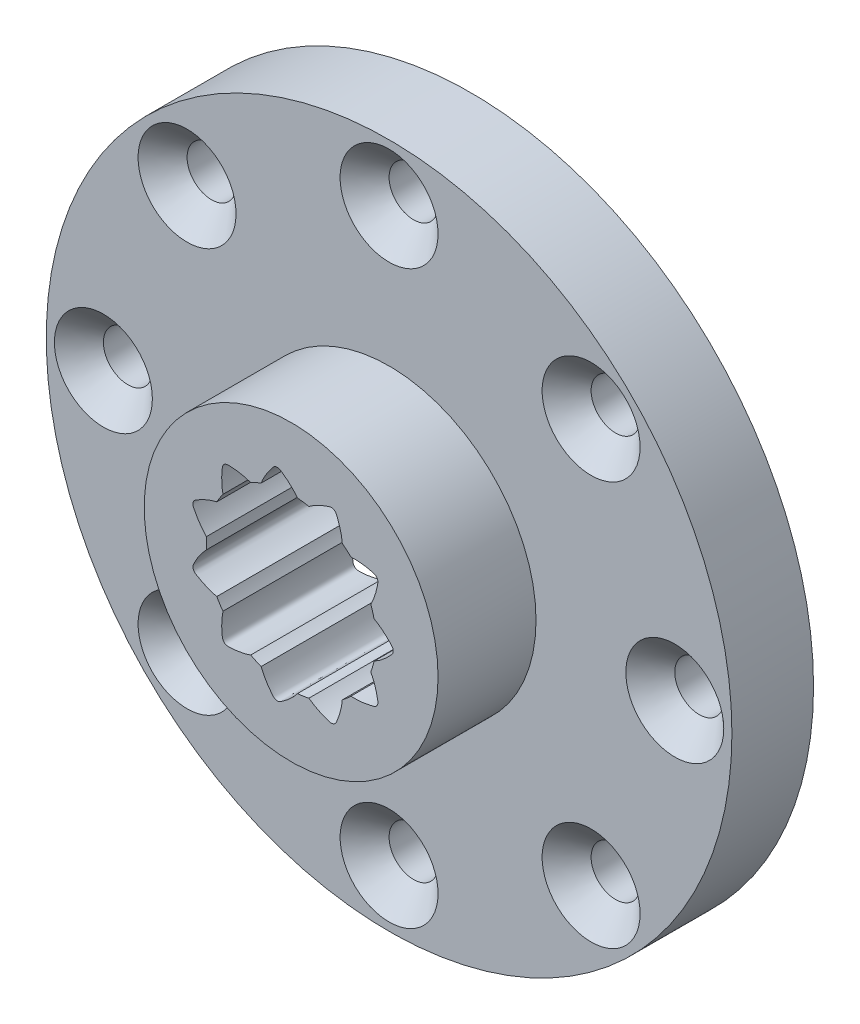
SolidWorks part; units mm, degrees
material "合金钢"
ref_plane "前视基准面" through (0, 0, 0) normal (0, 0, 1) x (1, 0, 0)
ref_plane "上视基准面" through (0, 0, 0) normal (0, 1, 0) x (1, 0, 0)
ref_plane "右视基准面" through (0, 0, 0) normal (1, 0, 0) x (0, 0, -1)
ref_axis "基准轴1" through (0, 0, 55) along (0, 0, -1)
sketch "旋转草图内花键" plane through (0, 0, 0) normal (1, 0, 0) x (0, 0, -1)
  line L0 (0, 0) -> (1, 0) construction
  line L1 (-12.7, 5.2) -> (-12.7, 19.05)
  line L2 (-12.7, 19.05) -> (12.7, 19.05)
  line L3 (12.7, 19.05) -> (12.7, 5.2)
  line L4 (12.7, 5.2) -> (-12.7, 5.2)
revolve "内花键" add sketch "旋转草图内花键" angle 360 about L0
sketch "齿草图内花键" plane through (0, 0, 0) normal (0, 0, 1) x (1, 0, 0)
  arc A0 (4.469, -1.3848) -> (4.469, 1.3848) centre (0, 0) ccw
  spline S0 degree 3 poles (4.469, 1.3848) (4.5766, 1.3527) (4.7413, 1.292) (4.9613, 1.1888) (5.1395, 1.0919) (5.3233, 0.9774) (5.5112, 0.8441) (5.7013, 0.6912) (5.8934, 0.5188) (6.0538, 0.3498) (6.1648, 0.2366) (6.2079, 0.1723) (6.2223, 0.1454) (6.2343, 0.1173) (6.2438, 0.0883) (6.257, 0.0305) (6.257, -0.0305) (6.2438, -0.0883) (6.2343, -0.1173) (6.2223, -0.1454) (6.2079, -0.1723) (6.1648, -0.2366) (6.0538, -0.3498) (5.8934, -0.5188) (5.7013, -0.6912) (5.5112, -0.8441) (5.3233, -0.9774) (5.1395, -1.0919) (4.9613, -1.1888) (4.7413, -1.292) (4.5766, -1.3527) (4.469, -1.3848) knots 0 0 0 0 0.072254 0.112805 0.156306 0.202756 0.252156 0.304505 0.359804 0.418052 0.454758 0.461299 0.467839 0.47438 0.48092 0.487461 0.512539 0.51908 0.52562 0.532161 0.538701 0.545242 0.581948 0.640196 0.695495 0.747844 0.797244 0.843694 0.887195 0.927746 1 1 1 1
extrude "齿拉伸切除内花键" cut sketch "齿草图内花键" against normal blind 12.7 and the other way blind 12.7
pattern_circular "齿形内花键" count 11 over 360 about axis through (0, 0, 55) along (0, 0, -1) of "齿拉伸切除内花键"
sketch "辅助草图内花键" plane through (0, 0, 0) normal (0, 0, 1) x (1, 0, 0)
  circle A0 centre (0, 0) radius 5.5 construction
  circle A1 centre (0, 0) radius 6.06 construction
  dimension "PitchDiameter" = 11
  dimension "FormDiameter" = 12.12
sketch "草图2" plane through (0, 0, -12.7) normal (0, 0, -1) x (-1, 0, 0)
  circle A0 centre (0, 0) radius 19.05 construction
  circle A1 centre (0, 0) radius 19.05
extrude "切除-拉伸1" cut sketch "草图2" against normal blind 16.4
sketch "草图3" plane through (0, 0, 3.7) normal (0, 0, -1) x (-1, 0, 0)
  circle A0 centre (0, 0) radius 14.5
  circle A1 centre (0, 0) radius 19.05
  dimension "D1" = 29
extrude "切除-拉伸3" cut sketch "草图3" against normal through all
sketch "草图4" plane through (0, 0, 12.7) normal (0, 0, 1) x (1, 0, 0)
  circle A0 centre (0, 0) radius 8
  circle A1 centre (0, 0) radius 14.5
  dimension "D1" = 16
extrude "切除-拉伸4" cut sketch "草图4" against normal blind 5
sketch "草图7" plane through (0, 0, 3.7) normal (0, 0, -1) x (-1, 0, 0)
  circle A1 centre (0, 0) radius 14.5
  circle A2 centre (0, 0) radius 14.5
  dimension "D1" = 0
extrude "切除-拉伸6" cut sketch "草图7" against normal blind 1
sketch "草图9" plane through (0, 0, 4.7) normal (0, 0, -1) x (-1, 0, 0)
  circle A0 centre (0, 0) radius 17.5 construction
  circle A1 centre (0, 17.5) radius 1.5
  circle A2 centre (12.3744, 12.3744) radius 1.5
  circle A3 centre (17.5, 0) radius 1.5
  circle A4 centre (12.3744, -12.3744) radius 1.5
  circle A5 centre (0, -17.5) radius 1.5
  circle A6 centre (-12.3744, -12.3744) radius 1.5
  circle A7 centre (-17.5, 0) radius 1.5
  circle A8 centre (-12.3744, 12.3744) radius 1.5
  circle A9 centre (0, 0) radius 21
  point P21 (0, 0)
  dimension "D1" = 35
  dimension "D2" = 3
  dimension "D4" = 42
  dimension "D3" = 8
extrude "凸台-拉伸1" add sketch "草图9" along normal blind 3
sketch "草图12" plane through (0, 0, 7.7) normal (0, 0, 1) x (1, 0, 0)
  circle A0 centre (0, 0) radius 8 construction
  circle A1 centre (0, 0) radius 14.5
  circle A2 centre (0, 0) radius 14.5
  circle A3 centre (0, 0) radius 8
  dimension "D1" = 0
extrude "切除-拉伸8" cut sketch "草图12" against normal up to surface (3 mm away) up to face at (10.8744, 12.3744, 4.7)
sketch "草图13" plane through (0, 0, 4.7) normal (0, 0, 1) x (1, 0, 0)
  arc A11 (-4.5541, -2.51) -> (-4.175, -3.0999) centre (0, 0) ccw
  arc A12 (-2.4742, -4.5737) -> (-1.8363, -4.865) centre (0, 0) ccw
  arc A13 (0.3913, -5.1853) -> (1.0854, -5.0855) centre (0, 0) ccw
  arc A14 (3.1326, -4.1505) -> (3.6625, -3.6914) centre (0, 0) ccw
  arc A15 (4.8792, -1.7981) -> (5.0768, -1.1253) centre (0, 0) ccw
  arc A16 (5.0768, 1.1253) -> (4.8792, 1.7981) centre (0, 0) ccw
  arc A17 (3.6625, 3.6914) -> (3.1326, 4.1505) centre (0, 0) ccw
  arc A18 (1.0854, 5.0855) -> (0.3913, 5.1853) centre (0, 0) ccw
  arc A19 (-1.8363, 4.865) -> (-2.4742, 4.5737) centre (0, 0) ccw
  arc A20 (-4.175, 3.0999) -> (-4.5541, 2.51) centre (0, 0) ccw
  arc A21 (-5.1882, 0.3506) -> (-5.1882, -0.3506) centre (0, 0) ccw
  arc A22 (-4.5541, -2.51) -> (-4.175, -3.0999) centre (0, 0) ccw
  arc A23 (-2.4742, -4.5737) -> (-1.8363, -4.865) centre (0, 0) ccw
  arc A24 (0.3913, -5.1853) -> (1.0854, -5.0855) centre (0, 0) ccw
  arc A25 (3.1326, -4.1505) -> (3.6625, -3.6914) centre (0, 0) ccw
  arc A26 (4.8792, -1.7981) -> (5.0768, -1.1253) centre (0, 0) ccw
  arc A27 (5.0768, 1.1253) -> (4.8792, 1.7981) centre (0, 0) ccw
  arc A28 (3.6625, 3.6914) -> (3.1326, 4.1505) centre (0, 0) ccw
  arc A29 (1.0854, 5.0855) -> (0.3913, 5.1853) centre (0, 0) ccw
  arc A30 (-1.8363, 4.865) -> (-2.4742, 4.5737) centre (0, 0) ccw
  arc A31 (-4.175, 3.0999) -> (-4.5541, 2.51) centre (0, 0) ccw
  arc A32 (-5.1882, 0.3506) -> (-5.1882, -0.3506) centre (0, 0) ccw
  spline S11 degree 3 poles (506.9828, -3964.9614) (126.511, -73.8344) (7.0446, 13.3904) (-5.383, -0.562) (-5.5258, -0.7427) (-5.6651, -0.9431) (-5.8009, -1.1625) (-5.9071, -1.37) (-5.9817, -1.5098) (-6.005, -1.5837) (-6.0112, -1.6136) (-6.0149, -1.6439) (-6.0157, -1.6744) (-6.0122, -1.7336) (-5.995, -1.792) (-5.966, -1.8438) (-5.9488, -1.869) (-5.9293, -1.8925) (-5.9079, -1.9143) (-5.8484, -1.9638) (-5.71, -2.0411) (-5.5085, -2.1582) (-5.2757, -2.2695) (-5.0501, -2.3626) (-4.8323, -2.4375) (13.1656, -7.4562) (66.5095, 130.5093) (-1717.0974, 3609.5914) knots -11.769614 -11.769614 -11.769614 -11.769614 0.156306 0.202756 0.252156 0.304505 0.359804 0.418052 0.454758 0.461299 0.467839 0.47438 0.48092 0.487461 0.512539 0.51908 0.52562 0.532161 0.538701 0.545242 0.581948 0.640196 0.695495 0.747844 0.797244 0.843694 12.769566 12.769566 12.769566 12.769566 only from (-5.1882, -0.3506) to (-4.5541, -2.51)
  spline S12 degree 3 poles (2570.1211, -3061.4422) (146.3457, 6.2836) (-1.3132, 15.0733) (-4.2246, -3.383) (-4.247, -3.6123) (-4.256, -3.8562) (-4.2515, -4.1142) (-4.2287, -4.3461) (-4.2159, -4.5041) (-4.1955, -4.5788) (-4.1846, -4.6073) (-4.1713, -4.6348) (-4.1555, -4.6609) (-4.1205, -4.7088) (-4.0745, -4.7487) (-4.0221, -4.7765) (-3.994, -4.7884) (-3.9649, -4.7977) (-3.9351, -4.8044) (-3.8583, -4.814) (-3.7001, -4.8042) (-3.4672, -4.7937) (-3.2112, -4.7614) (-2.9711, -4.7179) (-2.7474, -4.6631) (15.1067, 0.8453) (-14.6073, 145.7492) (-3396.0067, 2108.2486) knots -11.769614 -11.769614 -11.769614 -11.769614 0.156306 0.202756 0.252156 0.304505 0.359804 0.418052 0.454758 0.461299 0.467839 0.47438 0.48092 0.487461 0.512539 0.51908 0.52562 0.532161 0.538701 0.545242 0.581948 0.640196 0.695495 0.747844 0.797244 0.843694 12.769566 12.769566 12.769566 12.769566 only from (-4.175, -3.0999) to (-2.4742, -4.5737)
  spline S13 degree 3 poles (3817.2641, -1185.9367) (119.7167, 84.4065) (-9.254, 11.9705) (-1.725, -5.13) (-1.6199, -5.335) (-1.4956, -5.5449) (-1.3523, -5.7596) (-1.2077, -5.9424) (-1.1115, -6.0684) (-1.054, -6.1202) (-1.0294, -6.1383) (-1.0033, -6.1542) (-0.9759, -6.1676) (-0.9206, -6.189) (-0.8603, -6.1977) (-0.8012, -6.1928) (-0.7711, -6.1876) (-0.7417, -6.1797) (-0.713, -6.1692) (-0.6432, -6.1357) (-0.5153, -6.042) (-0.3252, -5.9073) (-0.1272, -5.7417) (0.0512, -5.5752) (0.2098, -5.4082) (12.2516, 8.8785) (-91.0864, 114.7147) (-3996.7079, -62.4482) knots -11.769614 -11.769614 -11.769614 -11.769614 0.156306 0.202756 0.252156 0.304505 0.359804 0.418052 0.454758 0.461299 0.467839 0.47438 0.48092 0.487461 0.512539 0.51908 0.52562 0.532161 0.538701 0.545242 0.581948 0.640196 0.695495 0.747844 0.797244 0.843694 12.769566 12.769566 12.769566 12.769566 only from (-1.8363, -4.865) to (0.3913, -5.1853)
  spline S14 degree 3 poles (3852.4527, 1066.0953) (55.0785, 135.731) (-14.2567, 5.0672) (1.3223, -5.2482) (1.5216, -5.3638) (1.7397, -5.4733) (1.9763, -5.5764) (2.1967, -5.652) (2.3457, -5.706) (2.4222, -5.7185) (2.4526, -5.7204) (2.4831, -5.7197) (2.5135, -5.7162) (2.5715, -5.7043) (2.627, -5.6789) (2.674, -5.6429) (2.6965, -5.6222) (2.7171, -5.5996) (2.7356, -5.5754) (2.7762, -5.5094) (2.833, -5.3614) (2.9202, -5.1453) (2.9972, -4.899) (3.0573, -4.6625) (3.1004, -4.4362) (5.5066, 14.0927) (-138.6462, 47.2591) (-3328.4825, -2213.3182) knots -11.769614 -11.769614 -11.769614 -11.769614 0.156306 0.202756 0.252156 0.304505 0.359804 0.418052 0.454758 0.461299 0.467839 0.47438 0.48092 0.487461 0.512539 0.51908 0.52562 0.532161 0.538701 0.545242 0.581948 0.640196 0.695495 0.747844 0.797244 0.843694 12.769566 12.769566 12.769566 12.769566 only from (1.0854, -5.0855) to (3.1326, -4.1505)
  spline S15 degree 3 poles (2664.5148, 2979.6496) (-27.0468, 143.9618) (-14.733, -3.445) (3.9498, -3.7002) (4.1799, -3.6897) (4.4226, -3.6639) (4.6773, -3.6227) (4.9037, -3.5672) (5.0582, -3.532) (5.1293, -3.5012) (5.156, -3.4863) (5.1812, -3.4692) (5.2049, -3.4499) (5.2473, -3.4084) (5.2802, -3.3572) (5.3003, -3.3014) (5.3081, -3.2719) (5.3131, -3.2418) (5.3156, -3.2113) (5.3141, -3.1339) (5.2819, -2.9787) (5.2384, -2.7497) (5.17, -2.5009) (5.0927, -2.2694) (5.0066, -2.0558) (-2.9866, 14.8326) (-142.1868, -35.2009) (-1603.4875, -3661.4753) knots -11.769614 -11.769614 -11.769614 -11.769614 0.156306 0.202756 0.252156 0.304505 0.359804 0.418052 0.454758 0.461299 0.467839 0.47438 0.48092 0.487461 0.512539 0.51908 0.52562 0.532161 0.538701 0.545242 0.581948 0.640196 0.695495 0.747844 0.797244 0.843694 12.769566 12.769566 12.769566 12.769566 only from (3.6625, -3.6914) to (4.8792, -1.7981)
  spline S16 degree 3 poles (630.6123, 3947.1862) (-100.5848, 106.4858) (-10.5317, -10.8634) (5.3233, -0.9774) (5.5112, -0.8441) (5.7013, -0.6912) (5.8934, -0.5188) (6.0538, -0.3498) (6.1648, -0.2366) (6.2079, -0.1723) (6.2223, -0.1454) (6.2343, -0.1173) (6.2438, -0.0883) (6.257, -0.0305) (6.257, 0.0305) (6.2438, 0.0883) (6.2343, 0.1173) (6.2223, 0.1454) (6.2079, 0.1723) (6.1648, 0.2366) (6.0538, 0.3498) (5.8934, 0.5188) (5.7013, 0.6912) (5.5112, 0.8441) (5.3233, 0.9774) (-10.5317, 10.8633) (-100.5841, -106.4849) (630.6034, -3947.1398) knots -11.769614 -11.769614 -11.769614 -11.769614 0.156306 0.202756 0.252156 0.304505 0.359804 0.418052 0.454758 0.461299 0.467839 0.47438 0.48092 0.487461 0.512539 0.51908 0.52562 0.532161 0.538701 0.545242 0.581948 0.640196 0.695495 0.747844 0.797244 0.843694 12.769566 12.769566 12.769566 12.769566 only from (5.0768, -1.1253) to (5.0768, 1.1253)
  spline S17 degree 3 poles (-1603.5052, 3661.5191) (-142.1879, 35.2013) (-2.9867, -14.8327) (5.0066, 2.0558) (5.0927, 2.2694) (5.17, 2.5009) (5.2384, 2.7497) (5.2819, 2.9787) (5.3141, 3.1339) (5.3156, 3.2113) (5.3131, 3.2418) (5.3081, 3.2719) (5.3003, 3.3014) (5.2802, 3.3572) (5.2473, 3.4084) (5.2049, 3.4499) (5.1812, 3.4692) (5.156, 3.4863) (5.1293, 3.5012) (5.0582, 3.532) (4.9037, 3.5672) (4.6773, 3.6227) (4.4226, 3.6639) (4.1799, 3.6897) (3.9498, 3.7002) (-14.733, 3.445) (-27.0467, -143.9607) (2664.4823, -2979.6154) knots -11.769614 -11.769614 -11.769614 -11.769614 0.156306 0.202756 0.252156 0.304505 0.359804 0.418052 0.454758 0.461299 0.467839 0.47438 0.48092 0.487461 0.512539 0.51908 0.52562 0.532161 0.538701 0.545242 0.581948 0.640196 0.695495 0.747844 0.797244 0.843694 12.769566 12.769566 12.769566 12.769566 only from (4.8792, 1.7981) to (3.6625, 3.6914)
  spline S18 degree 3 poles (-3328.5211, 2213.3455) (-138.6474, -47.2594) (5.5066, -14.0928) (3.1004, 4.4362) (3.0573, 4.6625) (2.9972, 4.899) (2.9202, 5.1453) (2.833, 5.3614) (2.7762, 5.5094) (2.7356, 5.5754) (2.7171, 5.5996) (2.6965, 5.6222) (2.674, 5.6429) (2.627, 5.6789) (2.5715, 5.7043) (2.5135, 5.7162) (2.4831, 5.7197) (2.4526, 5.7204) (2.4222, 5.7185) (2.3457, 5.706) (2.1967, 5.652) (1.9763, 5.5764) (1.7397, 5.4733) (1.5216, 5.3638) (1.3223, 5.2482) (-14.2566, -5.0672) (55.0779, -135.7299) (3852.4068, -1066.0841) knots -11.769614 -11.769614 -11.769614 -11.769614 0.156306 0.202756 0.252156 0.304505 0.359804 0.418052 0.454758 0.461299 0.467839 0.47438 0.48092 0.487461 0.512539 0.51908 0.52562 0.532161 0.538701 0.545242 0.581948 0.640196 0.695495 0.747844 0.797244 0.843694 12.769566 12.769566 12.769566 12.769566 only from (3.1326, 4.1505) to (1.0854, 5.0855)
  spline S19 degree 3 poles (-3996.755, 62.4504) (-91.0872, -114.7155) (12.2516, -8.8785) (0.2098, 5.4082) (0.0512, 5.5752) (-0.1272, 5.7417) (-0.3252, 5.9073) (-0.5153, 6.042) (-0.6432, 6.1357) (-0.713, 6.1692) (-0.7417, 6.1797) (-0.7711, 6.1876) (-0.8012, 6.1928) (-0.8603, 6.1977) (-0.9206, 6.189) (-0.9759, 6.1676) (-1.0033, 6.1542) (-1.0294, 6.1383) (-1.054, 6.1202) (-1.1115, 6.0684) (-1.2077, 5.9424) (-1.3523, 5.7596) (-1.4956, 5.5449) (-1.6199, 5.335) (-1.725, 5.13) (-9.2539, -11.9705) (119.7156, -84.4059) (3817.2194, 1185.9214) knots -11.769614 -11.769614 -11.769614 -11.769614 0.156306 0.202756 0.252156 0.304505 0.359804 0.418052 0.454758 0.461299 0.467839 0.47438 0.48092 0.487461 0.512539 0.51908 0.52562 0.532161 0.538701 0.545242 0.581948 0.640196 0.695495 0.747844 0.797244 0.843694 12.769566 12.769566 12.769566 12.769566 only from (0.3913, 5.1853) to (-1.8363, 4.865)
  spline S20 degree 3 poles (-3396.0475, -2108.2723) (-14.6076, -145.7503) (15.1068, -0.8454) (-2.7474, 4.6631) (-2.9711, 4.7179) (-3.2112, 4.7614) (-3.4672, 4.7937) (-3.7001, 4.8042) (-3.8583, 4.814) (-3.9351, 4.8044) (-3.9649, 4.7977) (-3.994, 4.7884) (-4.0221, 4.7765) (-4.0745, 4.7487) (-4.1205, 4.7088) (-4.1555, 4.6609) (-4.1713, 4.6348) (-4.1846, 4.6073) (-4.1955, 4.5788) (-4.2159, 4.5041) (-4.2287, 4.3461) (-4.2515, 4.1142) (-4.256, 3.8562) (-4.247, 3.6123) (-4.2246, 3.383) (-1.3132, -15.0733) (146.3445, -6.2836) (2570.0918, 3061.4052) knots -11.769614 -11.769614 -11.769614 -11.769614 0.156306 0.202756 0.252156 0.304505 0.359804 0.418052 0.454758 0.461299 0.467839 0.47438 0.48092 0.487461 0.512539 0.51908 0.52562 0.532161 0.538701 0.545242 0.581948 0.640196 0.695495 0.747844 0.797244 0.843694 12.769566 12.769566 12.769566 12.769566 only from (-2.4742, 4.5737) to (-4.175, 3.0999)
  spline S21 degree 3 poles (-1717.1189, -3609.6334) (66.5099, -130.5104) (13.1657, 7.4562) (-4.8323, 2.4375) (-5.0501, 2.3626) (-5.2757, 2.2695) (-5.5085, 2.1582) (-5.71, 2.0411) (-5.8484, 1.9638) (-5.9079, 1.9143) (-5.9293, 1.8925) (-5.9488, 1.869) (-5.966, 1.8438) (-5.995, 1.792) (-6.0122, 1.7336) (-6.0157, 1.6744) (-6.0149, 1.6439) (-6.0112, 1.6136) (-6.005, 1.5837) (-5.9817, 1.5098) (-5.9071, 1.37) (-5.8009, 1.1625) (-5.6651, 0.9431) (-5.5258, 0.7427) (-5.383, 0.562) (7.0445, -13.3904) (126.51, 73.8337) (506.9782, 3964.9145) knots -11.769614 -11.769614 -11.769614 -11.769614 0.156306 0.202756 0.252156 0.304505 0.359804 0.418052 0.454758 0.461299 0.467839 0.47438 0.48092 0.487461 0.512539 0.51908 0.52562 0.532161 0.538701 0.545242 0.581948 0.640196 0.695495 0.747844 0.797244 0.843694 12.769566 12.769566 12.769566 12.769566 only from (-4.5541, 2.51) to (-5.1882, 0.3506)
  spline S22 degree 3 poles (-5.1882, -0.3506) (-5.2037, -0.3664) (-5.2692, -0.4342) (-5.383, -0.562) (-5.5258, -0.7427) (-5.6651, -0.9431) (-5.8009, -1.1625) (-5.9071, -1.37) (-5.9817, -1.5098) (-6.005, -1.5837) (-6.0112, -1.6136) (-6.0149, -1.6439) (-6.0157, -1.6744) (-6.0122, -1.7336) (-5.995, -1.792) (-5.966, -1.8438) (-5.9488, -1.869) (-5.9293, -1.8925) (-5.9079, -1.9143) (-5.8484, -1.9638) (-5.71, -2.0411) (-5.5085, -2.1582) (-5.2757, -2.2695) (-5.0501, -2.3626) (-4.8323, -2.4375) (-4.6675, -2.4835) (-4.5757, -2.5051) (-4.5541, -2.51) knots 0.142067 0.142067 0.142067 0.142067 0.156306 0.202756 0.252156 0.304505 0.359804 0.418052 0.454758 0.461299 0.467839 0.47438 0.48092 0.487461 0.512539 0.51908 0.52562 0.532161 0.538701 0.545242 0.581948 0.640196 0.695495 0.747844 0.797244 0.843694 0.857933 0.857933 0.857933 0.857933
  spline S23 degree 3 poles (-4.175, -3.0999) (-4.1795, -3.1215) (-4.198, -3.214) (-4.2246, -3.383) (-4.247, -3.6123) (-4.256, -3.8562) (-4.2515, -4.1142) (-4.2287, -4.3461) (-4.2159, -4.5041) (-4.1955, -4.5788) (-4.1846, -4.6073) (-4.1713, -4.6348) (-4.1555, -4.6609) (-4.1205, -4.7088) (-4.0745, -4.7487) (-4.0221, -4.7765) (-3.994, -4.7884) (-3.9649, -4.7977) (-3.9351, -4.8044) (-3.8583, -4.814) (-3.7001, -4.8042) (-3.4672, -4.7937) (-3.2112, -4.7614) (-2.9711, -4.7179) (-2.7474, -4.6631) (-2.5839, -4.6126) (-2.4949, -4.5812) (-2.4742, -4.5737) knots 0.142067 0.142067 0.142067 0.142067 0.156306 0.202756 0.252156 0.304505 0.359804 0.418052 0.454758 0.461299 0.467839 0.47438 0.48092 0.487461 0.512539 0.51908 0.52562 0.532161 0.538701 0.545242 0.581948 0.640196 0.695495 0.747844 0.797244 0.843694 0.857933 0.857933 0.857933 0.857933
  spline S24 degree 3 poles (-1.8363, -4.865) (-1.8284, -4.8856) (-1.7939, -4.9734) (-1.725, -5.13) (-1.6199, -5.335) (-1.4956, -5.5449) (-1.3523, -5.7596) (-1.2077, -5.9424) (-1.1115, -6.0684) (-1.054, -6.1202) (-1.0294, -6.1383) (-1.0033, -6.1542) (-0.9759, -6.1676) (-0.9206, -6.189) (-0.8603, -6.1977) (-0.8012, -6.1928) (-0.7711, -6.1876) (-0.7417, -6.1797) (-0.713, -6.1692) (-0.6432, -6.1357) (-0.5153, -6.042) (-0.3252, -5.9073) (-0.1272, -5.7417) (0.0512, -5.5752) (0.2098, -5.4082) (0.3201, -5.2773) (0.3779, -5.2029) (0.3913, -5.1853) knots 0.142067 0.142067 0.142067 0.142067 0.156306 0.202756 0.252156 0.304505 0.359804 0.418052 0.454758 0.461299 0.467839 0.47438 0.48092 0.487461 0.512539 0.51908 0.52562 0.532161 0.538701 0.545242 0.581948 0.640196 0.695495 0.747844 0.797244 0.843694 0.857933 0.857933 0.857933 0.857933
  spline S25 degree 3 poles (1.0854, -5.0855) (1.1032, -5.0986) (1.1797, -5.1537) (1.3223, -5.2482) (1.5216, -5.3638) (1.7397, -5.4733) (1.9763, -5.5764) (2.1967, -5.652) (2.3457, -5.706) (2.4222, -5.7185) (2.4526, -5.7204) (2.4831, -5.7197) (2.5135, -5.7162) (2.5715, -5.7043) (2.627, -5.6789) (2.674, -5.6429) (2.6965, -5.6222) (2.7171, -5.5996) (2.7356, -5.5754) (2.7762, -5.5094) (2.833, -5.3614) (2.9202, -5.1453) (2.9972, -4.899) (3.0573, -4.6625) (3.1004, -4.4362) (3.1224, -4.2665) (3.1308, -4.1726) (3.1326, -4.1505) knots 0.142067 0.142067 0.142067 0.142067 0.156306 0.202756 0.252156 0.304505 0.359804 0.418052 0.454758 0.461299 0.467839 0.47438 0.48092 0.487461 0.512539 0.51908 0.52562 0.532161 0.538701 0.545242 0.581948 0.640196 0.695495 0.747844 0.797244 0.843694 0.857933 0.857933 0.857933 0.857933
  spline S26 degree 3 poles (3.6625, -3.6914) (3.6846, -3.6928) (3.7787, -3.6978) (3.9498, -3.7002) (4.1799, -3.6897) (4.4226, -3.6639) (4.6773, -3.6227) (4.9037, -3.5672) (5.0582, -3.532) (5.1293, -3.5012) (5.156, -3.4863) (5.1812, -3.4692) (5.2049, -3.4499) (5.2473, -3.4084) (5.2802, -3.3572) (5.3003, -3.3014) (5.3081, -3.2719) (5.3131, -3.2418) (5.3156, -3.2113) (5.3141, -3.1339) (5.2819, -2.9787) (5.2384, -2.7497) (5.17, -2.5009) (5.0927, -2.2694) (5.0066, -2.0558) (4.9334, -1.9011) (4.8897, -1.8176) (4.8792, -1.7981) knots 0.142067 0.142067 0.142067 0.142067 0.156306 0.202756 0.252156 0.304505 0.359804 0.418052 0.454758 0.461299 0.467839 0.47438 0.48092 0.487461 0.512539 0.51908 0.52562 0.532161 0.538701 0.545242 0.581948 0.640196 0.695495 0.747844 0.797244 0.843694 0.857933 0.857933 0.857933 0.857933
  spline S27 degree 3 poles (5.0768, -1.1253) (5.0961, -1.1145) (5.1781, -1.0679) (5.3233, -0.9774) (5.5112, -0.8441) (5.7013, -0.6912) (5.8934, -0.5188) (6.0538, -0.3498) (6.1648, -0.2366) (6.2079, -0.1723) (6.2223, -0.1454) (6.2343, -0.1173) (6.2438, -0.0883) (6.257, -0.0305) (6.257, 0.0305) (6.2438, 0.0883) (6.2343, 0.1173) (6.2223, 0.1454) (6.2079, 0.1723) (6.1648, 0.2366) (6.0538, 0.3498) (5.8934, 0.5188) (5.7013, 0.6912) (5.5112, 0.8441) (5.3233, 0.9774) (5.1781, 1.0679) (5.0961, 1.1145) (5.0768, 1.1253) knots 0.142067 0.142067 0.142067 0.142067 0.156306 0.202756 0.252156 0.304505 0.359804 0.418052 0.454758 0.461299 0.467839 0.47438 0.48092 0.487461 0.512539 0.51908 0.52562 0.532161 0.538701 0.545242 0.581948 0.640196 0.695495 0.747844 0.797244 0.843694 0.857933 0.857933 0.857933 0.857933
  spline S28 degree 3 poles (4.8792, 1.7981) (4.8897, 1.8176) (4.9334, 1.9011) (5.0066, 2.0558) (5.0927, 2.2694) (5.17, 2.5009) (5.2384, 2.7497) (5.2819, 2.9787) (5.3141, 3.1339) (5.3156, 3.2113) (5.3131, 3.2418) (5.3081, 3.2719) (5.3003, 3.3014) (5.2802, 3.3572) (5.2473, 3.4084) (5.2049, 3.4499) (5.1812, 3.4692) (5.156, 3.4863) (5.1293, 3.5012) (5.0582, 3.532) (4.9037, 3.5672) (4.6773, 3.6227) (4.4226, 3.6639) (4.1799, 3.6897) (3.9498, 3.7002) (3.7787, 3.6978) (3.6846, 3.6928) (3.6625, 3.6914) knots 0.142067 0.142067 0.142067 0.142067 0.156306 0.202756 0.252156 0.304505 0.359804 0.418052 0.454758 0.461299 0.467839 0.47438 0.48092 0.487461 0.512539 0.51908 0.52562 0.532161 0.538701 0.545242 0.581948 0.640196 0.695495 0.747844 0.797244 0.843694 0.857933 0.857933 0.857933 0.857933
  spline S29 degree 3 poles (3.1326, 4.1505) (3.1308, 4.1726) (3.1224, 4.2665) (3.1004, 4.4362) (3.0573, 4.6625) (2.9972, 4.899) (2.9202, 5.1453) (2.833, 5.3614) (2.7762, 5.5094) (2.7356, 5.5754) (2.7171, 5.5996) (2.6965, 5.6222) (2.674, 5.6429) (2.627, 5.6789) (2.5715, 5.7043) (2.5135, 5.7162) (2.4831, 5.7197) (2.4526, 5.7204) (2.4222, 5.7185) (2.3457, 5.706) (2.1967, 5.652) (1.9763, 5.5764) (1.7397, 5.4733) (1.5216, 5.3638) (1.3223, 5.2482) (1.1797, 5.1537) (1.1032, 5.0986) (1.0854, 5.0855) knots 0.142067 0.142067 0.142067 0.142067 0.156306 0.202756 0.252156 0.304505 0.359804 0.418052 0.454758 0.461299 0.467839 0.47438 0.48092 0.487461 0.512539 0.51908 0.52562 0.532161 0.538701 0.545242 0.581948 0.640196 0.695495 0.747844 0.797244 0.843694 0.857933 0.857933 0.857933 0.857933
  spline S30 degree 3 poles (0.3913, 5.1853) (0.3779, 5.2029) (0.3201, 5.2773) (0.2098, 5.4082) (0.0512, 5.5752) (-0.1272, 5.7417) (-0.3252, 5.9073) (-0.5153, 6.042) (-0.6432, 6.1357) (-0.713, 6.1692) (-0.7417, 6.1797) (-0.7711, 6.1876) (-0.8012, 6.1928) (-0.8603, 6.1977) (-0.9206, 6.189) (-0.9759, 6.1676) (-1.0033, 6.1542) (-1.0294, 6.1383) (-1.054, 6.1202) (-1.1115, 6.0684) (-1.2077, 5.9424) (-1.3523, 5.7596) (-1.4956, 5.5449) (-1.6199, 5.335) (-1.725, 5.13) (-1.7939, 4.9734) (-1.8284, 4.8856) (-1.8363, 4.865) knots 0.142067 0.142067 0.142067 0.142067 0.156306 0.202756 0.252156 0.304505 0.359804 0.418052 0.454758 0.461299 0.467839 0.47438 0.48092 0.487461 0.512539 0.51908 0.52562 0.532161 0.538701 0.545242 0.581948 0.640196 0.695495 0.747844 0.797244 0.843694 0.857933 0.857933 0.857933 0.857933
  spline S31 degree 3 poles (-2.4742, 4.5737) (-2.4949, 4.5812) (-2.5839, 4.6126) (-2.7474, 4.6631) (-2.9711, 4.7179) (-3.2112, 4.7614) (-3.4672, 4.7937) (-3.7001, 4.8042) (-3.8583, 4.814) (-3.9351, 4.8044) (-3.9649, 4.7977) (-3.994, 4.7884) (-4.0221, 4.7765) (-4.0745, 4.7487) (-4.1205, 4.7088) (-4.1555, 4.6609) (-4.1713, 4.6348) (-4.1846, 4.6073) (-4.1955, 4.5788) (-4.2159, 4.5041) (-4.2287, 4.3461) (-4.2515, 4.1142) (-4.256, 3.8562) (-4.247, 3.6123) (-4.2246, 3.383) (-4.198, 3.214) (-4.1795, 3.1215) (-4.175, 3.0999) knots 0.142067 0.142067 0.142067 0.142067 0.156306 0.202756 0.252156 0.304505 0.359804 0.418052 0.454758 0.461299 0.467839 0.47438 0.48092 0.487461 0.512539 0.51908 0.52562 0.532161 0.538701 0.545242 0.581948 0.640196 0.695495 0.747844 0.797244 0.843694 0.857933 0.857933 0.857933 0.857933
  spline S32 degree 3 poles (-4.5541, 2.51) (-4.5757, 2.5051) (-4.6675, 2.4835) (-4.8323, 2.4375) (-5.0501, 2.3626) (-5.2757, 2.2695) (-5.5085, 2.1582) (-5.71, 2.0411) (-5.8484, 1.9638) (-5.9079, 1.9143) (-5.9293, 1.8925) (-5.9488, 1.869) (-5.966, 1.8438) (-5.995, 1.792) (-6.0122, 1.7336) (-6.0157, 1.6744) (-6.0149, 1.6439) (-6.0112, 1.6136) (-6.005, 1.5837) (-5.9817, 1.5098) (-5.9071, 1.37) (-5.8009, 1.1625) (-5.6651, 0.9431) (-5.5258, 0.7427) (-5.383, 0.562) (-5.2692, 0.4342) (-5.2037, 0.3664) (-5.1882, 0.3506) knots 0.142067 0.142067 0.142067 0.142067 0.156306 0.202756 0.252156 0.304505 0.359804 0.418052 0.454758 0.461299 0.467839 0.47438 0.48092 0.487461 0.512539 0.51908 0.52562 0.532161 0.538701 0.545242 0.581948 0.640196 0.695495 0.747844 0.797244 0.843694 0.857933 0.857933 0.857933 0.857933
  dimension "D1" = 0
extrude "切除-拉伸9" cut sketch "草图13" against normal blind 3
sketch "草图15" plane through (0, 0, 4.7) normal (0, 0, 1) x (1, 0, 0)
  circle A0 centre (12.3744, 12.3744) radius 1.5 construction
  circle A1 centre (0, 0) radius 21
  circle A2 centre (0, 0) radius 21
  circle A3 centre (17.5, 0) radius 1.5 construction
  circle A4 centre (12.3744, -12.3744) radius 1.5 construction
  circle A5 centre (0, -17.5) radius 1.5 construction
  circle A6 centre (-12.3744, -12.3744) radius 1.5 construction
  circle A7 centre (-17.5, 0) radius 1.5 construction
  circle A8 centre (-12.3744, 12.3744) radius 1.5 construction
  circle A9 centre (0, 17.5) radius 1.5 construction
  circle A10 centre (0, 0) radius 8 construction
  circle A11 centre (12.3744, 12.3744) radius 1.5
  circle A12 centre (17.5, 0) radius 1.5
  circle A13 centre (12.3744, -12.3744) radius 1.5
  circle A14 centre (0, -17.5) radius 1.5
  circle A15 centre (-12.3744, -12.3744) radius 1.5
  circle A16 centre (-17.5, 0) radius 1.5
  circle A17 centre (-12.3744, 12.3744) radius 1.5
  circle A18 centre (0, 17.5) radius 1.5
  circle A19 centre (0, 0) radius 8
  dimension "D1" = 0
extrude "凸台-拉伸2" add sketch "草图15" along normal blind 2
sketch "草图16" plane through (0, 0, 1.7) normal (0, 0, -1) x (-1, 0, 0)
  circle A0 centre (0, 0) radius 15
  dimension "D1" = 30
extrude "切除-拉伸10" cut sketch "草图16" against normal blind 3
sketch "草图17" plane through (0, 0, 6.7) normal (0, 0, 1) x (1, 0, 0)
  circle A0 centre (0, 0) radius 8
  circle A1 centre (0, 0) radius 9
  dimension "D1" = 18
extrude "凸台-拉伸4" add sketch "草图17" along normal blind 6
chamfer "倒角1" distance 1.5 angle 45 8 edges at (-10.8744, 12.3744, 6.7) (-16, 0, 6.7) (-10.8744, -12.3744, 6.7) (1.5, -17.5, 6.7) (13.8744, -12.3744, 6.7) (19, 0, 6.7) (13.8744, 12.3744, 6.7) (1.5, 17.5, 6.7)
